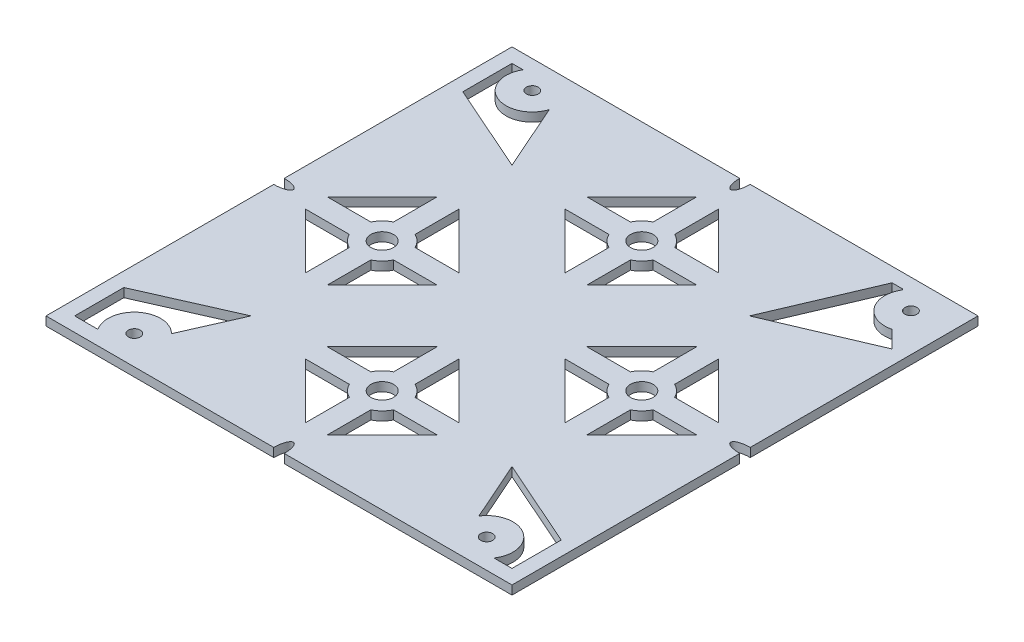
SolidWorks part; units mm, degrees
material "ABS"
ref_plane "Front Plane" through (0, 0, 0) normal (0, 0, 1) x (1, 0, 0)
ref_plane "Top Plane" through (0, 0, 0) normal (0, 1, 0) x (1, 0, 0)
ref_plane "Right Plane" through (0, 0, 0) normal (1, 0, 0) x (0, 0, -1)
sketch "Sketch1" plane through (0, 0, 0) normal (0, 1, 0) x (1, 0, 0)
  line L1 (0, 0) -> (97.6, 0)
  line L2 (0, 0) -> (0, 97.6)
  line L3 (0, 97.6) -> (97.6, 97.6)
  line L4 (97.6, 0) -> (97.6, 97.6)
  dimension "D1" = 97.6
  dimension "D2" = 97.6
extrude "Boss-Extrude1" add sketch "Sketch1" along normal blind 1.85
sketch "Sketch2" plane through (0, 0, 0) normal (0, -1, 0) x (-1, 0, 0)
  line L0 (-97.6, 97.6) -> (0, 0) construction
  line L1 (-97.6, 0) -> (0, 97.6) construction
  line L2 (-48.8, 97.6) -> (-48.8, 0) construction
  line L3 (-97.6, 97.6) -> (0, 97.6) construction
  line L4 (0, 0) -> (-97.6, 0) construction
  line L5 (-97.6, 48.8) -> (0, 48.8) construction
  line L6 (-97.6, 0) -> (-97.6, 97.6) construction
  line L7 (0, 97.6) -> (0, 0) construction
sketch "Sketch3" plane through (0, 0, 0) normal (0, -1, 0) x (1, 0, 0)
  line L0 (97.6, -97.6) -> (0, -97.6) construction
  line L1 (97.6, 0) -> (97.6, -97.6) construction
  line L2 (0, -97.6) -> (0, 0) construction
  line L3 (0, 0) -> (97.6, 0) construction
  line L4 (97.6, -94.6) -> (0, -94.6) construction
  line L5 (3, -97.6) -> (3, 0) construction
  line L6 (3, -94.6) -> (5.3161, -94.6)
  line L7 (3, -94.6) -> (3, -84.3)
  line L8 (3, -84.3) -> (21.4728, -76.1272)
  line L9 (97.6, 0) -> (0, -97.6) construction
  line L10 (21.4728, -76.1272) -> (13.3, -94.6)
  line L11 (21.4728, -21.4728) -> (13.3, -3)
  line L12 (3, -3) -> (13.3, -3)
  line L13 (0, -3) -> (97.6, -3) construction
  line L14 (3, -13.3) -> (3, -3)
  line L15 (3, -3) -> (7.8732, -3)
  line L16 (3, -13.3) -> (21.4728, -21.4728)
  line L17 (97.6, -97.6) -> (0, 0) construction
  line L18 (0, -97.6) -> (0, 0) construction
  line L19 (16.1614, -10.109) -> (21.4728, -21.4728) construction
  line L20 (94.6, -97.6) -> (94.6, 0) construction
  line L21 (94.6, -3) -> (94.6, -13.3)
  line L22 (94.6, -3) -> (84.3, -3)
  line L23 (94.6, -13.3) -> (76.1272, -21.4728)
  line L24 (76.1272, -21.4728) -> (84.3, -3)
  line L25 (94.6, -82.6) -> (73.6741, -73.6741)
  line L26 (73.6741, -73.6741) -> (82.6, -94.6)
  line L27 (94.6, -82.6) -> (82.6, -94.6) construction
  line L28 (94.6, -82.6) -> (91.0273, -86.1727)
  line L29 (82.6, -94.6) -> (85.1169, -94.6)
  line L30 (3, -94.6) -> (13.3, -94.6) construction
  circle A0 centre (89.66, -91.5) radius 1.25
  circle A1 centre (10.05, -91.8) radius 1.25
  circle A2 centre (12.45, -6.05) radius 1.25
  circle A3 centre (86.25, -6.05) radius 1.25
  circle A4 centre (89.66, -91.5) radius 5.5
  circle A5 centre (10.05, -91.8) radius 5.5
  circle A6 centre (12.45, -6.05) radius 5.5
  circle A7 centre (86.25, -6.05) radius 5.5
  dimension "D1" = 6.1
  dimension "D9" = 3
  dimension "D16" = 3
  dimension "D20" = 2.5
  dimension "D21" = 11
  dimension "D23" = 11
  dimension "D24" = 2.5
  dimension "D26" = 11
  dimension "D27" = 11
  dimension "D2" = 7.94
  dimension "D3" = 5.8
  dimension "D4" = 10.05
  dimension "D5" = 6.05
  dimension "D6" = 12.45
  dimension "D7" = 6.05
  dimension "D8" = 11.35
  dimension "D10" = 3
  dimension "D11" = 10.3
  dimension "D12" = 20.2
  dimension "D13" = 3
  dimension "D14" = 10.3
  dimension "D15" = 20.2
  dimension "D17" = 10.3
  dimension "D18" = 22.75
  dimension "D19" = 15
  dimension "D22" = 10.3
  dimension "D25" = 20.2
extrude "Cut-Extrude1" cut sketch "Sketch3" against normal blind 10 contours A2 | A1 | A1 | A5 L8 L7 L6 | A4 L28 L25 L26 L29 | A3 | A7 L24 L23 L21 L22 | A6 L15 L14 L16 | A0 region at (11.5662, 0, -84.2704) region at (10.6634, 0, -12.5774) region at (86.5986, 0, -12.9459) region at (83.266, 0, -83.1897) region at (10.05, 0, -91.8) region at (12.45, 0, -6.05) region at (86.25, 0, -6.05)
fillet "Fillet1" radius 0.2 1 edges at (85.1169, 0.925, -94.6)
sketch "Sketch5" plane through (0, 0, 0) normal (0, -1, 0) x (1, 0, 0)
  line L0 (78.0601, -69.3344) -> (24.4532, -15.7275) construction
  line L1 (15.9101, -24.6358) -> (67.2589, -75.9846) construction
  line L2 (97.6, -97.6) -> (0, 0) construction
  line L3 (25.594, -80.7317) -> (80.9701, -25.3556) construction
  line L4 (71.5743, -17.3) -> (16.8047, -72.0696) construction
  line L5 (97.6, 0) -> (0, -97.6) construction
  line L6 (51.05, -89.7671) -> (51.05, -80.6171)
  line L7 (46.55, -89.7671) -> (46.55, -80.6171)
  line L8 (48.8, -97.6) -> (48.8, 0) construction
  line L9 (51.05, -89.7671) -> (62.5825, -78.2346)
  line L10 (62.5825, -78.2346) -> (53.4325, -78.2346)
  line L11 (44.1675, -78.2346) -> (35.0175, -78.2346)
  line L12 (35.0175, -78.2346) -> (46.55, -89.7671)
  line L13 (48.8, -78.2346) -> (36.0473, -78.2346) construction
  line L14 (48.8, -73.7346) -> (36.0473, -73.7346) construction
  line L15 (44.1675, -73.7346) -> (35.0175, -73.7346)
  line L16 (46.55, -71.3521) -> (46.55, -62.2021)
  line L17 (53.4325, -73.7346) -> (62.5825, -73.7346)
  line L18 (51.05, -71.3521) -> (51.05, -62.2021)
  line L19 (62.5825, -73.7346) -> (51.05, -62.2021)
  line L20 (46.55, -62.2021) -> (35.0175, -73.7346)
  line L21 (48.8, -48.8) -> (-2.5605, -100.1605) construction
  line L22 (48.8, -48.8) -> (97.6, 0) construction
  line L23 (97.6, -97.6) -> (0, 0) construction
  line L24 (73.7346, -48.8) -> (73.7346, -36.0473) construction
  line L25 (78.2346, -48.8) -> (78.2346, -36.0473) construction
  line L26 (62.2021, -46.55) -> (73.7346, -35.0175)
  line L27 (73.7346, -62.5825) -> (62.2021, -51.05)
  line L28 (71.3521, -51.05) -> (62.2021, -51.05)
  line L29 (73.7346, -53.4325) -> (73.7346, -62.5825)
  line L30 (71.3521, -46.55) -> (62.2021, -46.55)
  line L31 (73.7346, -44.1675) -> (73.7346, -35.0175)
  line L32 (78.2346, -35.0175) -> (89.7671, -46.55)
  line L33 (78.2346, -44.1675) -> (78.2346, -35.0175)
  line L34 (78.2346, -62.5825) -> (78.2346, -53.4325)
  line L35 (89.7671, -51.05) -> (78.2346, -62.5825)
  line L36 (89.7671, -46.55) -> (80.6171, -46.55)
  line L37 (89.7671, -51.05) -> (80.6171, -51.05)
  line L38 (48.8, -19.3654) -> (61.5527, -19.3654) construction
  line L39 (48.8, -23.8654) -> (61.5527, -23.8654) construction
  line L40 (23.8654, -48.8) -> (23.8654, -61.5527) construction
  line L41 (19.3654, -48.8) -> (19.3654, -61.5527) construction
  line L42 (46.55, -7.8329) -> (46.55, -16.9829)
  line L43 (51.05, -7.8329) -> (51.05, -16.9829)
  line L44 (46.55, -7.8329) -> (35.0175, -19.3654)
  line L45 (35.0175, -19.3654) -> (44.1675, -19.3654)
  line L46 (53.4325, -19.3654) -> (62.5825, -19.3654)
  line L47 (62.5825, -19.3654) -> (51.05, -7.8329)
  line L48 (53.4325, -23.8654) -> (62.5825, -23.8654)
  line L49 (51.05, -26.2479) -> (51.05, -35.3979)
  line L50 (44.1675, -23.8654) -> (35.0175, -23.8654)
  line L51 (46.55, -26.2479) -> (46.55, -35.3979)
  line L52 (35.0175, -23.8654) -> (46.55, -35.3979)
  line L53 (51.05, -35.3979) -> (62.5825, -23.8654)
  line L54 (35.3979, -51.05) -> (23.8654, -62.5825)
  line L55 (23.8654, -35.0175) -> (35.3979, -46.55)
  line L56 (26.2479, -46.55) -> (35.3979, -46.55)
  line L57 (23.8654, -44.1675) -> (23.8654, -35.0175)
  line L58 (26.2479, -51.05) -> (35.3979, -51.05)
  line L59 (23.8654, -53.4325) -> (23.8654, -62.5825)
  line L60 (19.3654, -62.5825) -> (7.8329, -51.05)
  line L61 (19.3654, -53.4325) -> (19.3654, -62.5825)
  line L62 (19.3654, -35.0175) -> (19.3654, -44.1675)
  line L63 (7.8329, -46.55) -> (19.3654, -35.0175)
  line L64 (7.8329, -51.05) -> (16.9829, -51.05)
  line L65 (7.8329, -46.55) -> (16.9829, -46.55)
  line L66 (49.9, -97.6) -> (47.7, -97.6)
  line L67 (97.6, -97.6) -> (0, -97.6) construction
  line L68 (97.6, -48.8) -> (97.6, -49.9)
  line L69 (97.6, 0) -> (97.6, -97.6) construction
  line L70 (97.6, -48.8) -> (97.6, -47.7)
  line L71 (0, -49.9) -> (0, -48.8)
  line L72 (0, -97.6) -> (0, 0) construction
  line L73 (0, -48.8) -> (0, -47.7)
  line L74 (48.8, 0) -> (49.9, 0)
  line L75 (0, 0) -> (97.6, 0) construction
  line L76 (48.8, 0) -> (47.7, 0)
  circle A0 centre (48.8, -75.9846) radius 2.375
  circle A1 centre (48.8, -75.9846) radius 5.15
  circle A2 centre (75.9846, -48.8) radius 5.15
  circle A3 centre (75.9846, -48.8) radius 2.375
  circle A4 centre (48.8, -21.6154) radius 2.375
  circle A5 centre (48.8, -21.6154) radius 5.15
  circle A6 centre (21.6154, -48.8) radius 5.15
  circle A7 centre (21.6154, -48.8) radius 2.375
  ellipse E0 centre (48.8, -97.6) end of major axis (48.8, -94.6046) minor radius 1.1
  ellipse E1 centre (97.6, -48.8) end of major axis (94.5962, -48.8) minor radius 1.1
  ellipse E2 centre (0, -48.8) end of major axis (3, -48.8) minor radius 1.1
  ellipse E3 centre (48.8, 0) end of major axis (48.8, -3) minor radius 1.1
  line M15 (0, 0) -> (0, -97.6)
  line M16 (0, -97.6) -> (97.6, -97.6)
  line M17 (97.6, -97.6) -> (97.6, 0)
  line M18 (97.6, 0) -> (0, 0)
  dimension "D5" = 9.15
  dimension "D7" = 4.75
  dimension "D8" = 10.3
  dimension "D1" = 6.17
  dimension "D2" = 6.17
  dimension "D3" = 6.17
  dimension "D4" = 6.17
  dimension "D6" = 2.25
  dimension "D9" = 2.25
  dimension "D10" = 1.1
  dimension "D11" = 1.1
  dimension "D12" = 1.1
  dimension "D13" = 3
  dimension "D14" = 2.25
  dimension "D15" = 2.25
  dimension "D16" = 3
extrude "Cut-Extrude2" cut sketch "Sketch5" against normal blind 10 contours A1 L6 L9 L10 | A1 L11 L12 L7 | A0 | A1 L17 L19 L18 | A1 L16 L20 L15 | L61 A6 L64 L60 | L58 A6 L59 L54 | L57 A6 L56 L55 | L65 A6 L62 L63 | A7 | A3 | L37 A2 L34 L35 | L29 A2 L28 L27 | L30 A2 L31 L26 | L33 A2 L36 L32 | A5 L42 L44 L45 | A5 L46 L47 L43 | A5 L49 L53 L48 | A5 L50 L52 L51 | E0 M16 | E3 M18 | E1 M17 | E2 M15 | A4 region at (55.0576, 0, -82.2422) region at (42.5424, 0, -82.2422) region at (42.5424, 0, -69.7269) region at (55.0576, 0, -69.7269) region at (69.7269, 0, -42.5424) region at (69.7269, 0, -55.0576) region at (82.2422, 0, -42.5424) region at (82.2422, 0, -55.0576) region at (42.5424, 0, -15.3578) region at (55.0576, 0, -15.3578) region at (42.5424, 0, -27.8731) region at (55.0576, 0, -27.8731) region at (27.8731, 0, -55.0576) region at (15.3578, 0, -55.0576) region at (27.8731, 0, -42.5424) region at (15.3578, 0, -42.5424) region at (48.8, 0, -96.3287) region at (96.3251, 0, -48.8) region at (1.2732, 0, -48.8) region at (48.8, 0, -1.2732) region at (48.8, 0, -75.9846) region at (75.9846, 0, -48.8) region at (21.6154, 0, -48.8)
